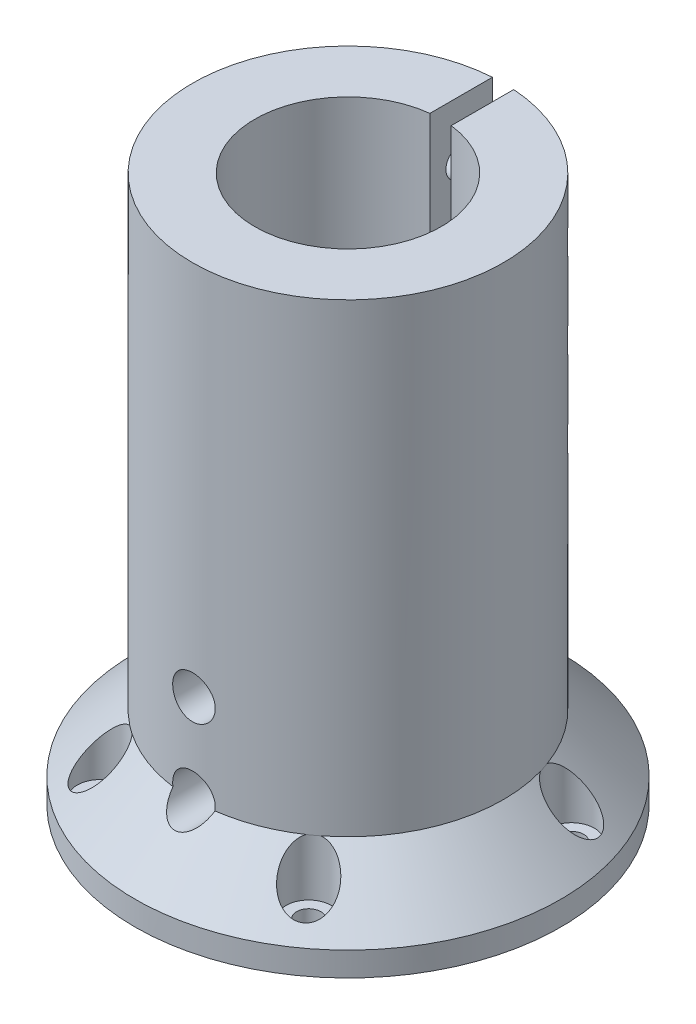
SolidWorks part; units mm, degrees
ref_plane "Front Plane" through (0, 0, 0) normal (0, 0, 1) x (1, 0, 0)
ref_plane "Top Plane" through (0, 0, 0) normal (0, 1, 0) x (1, 0, 0)
ref_plane "Right Plane" through (0, 0, 0) normal (1, 0, 0) x (0, 0, -1)
sketch "Sketch1" plane through (0, 0, 0) normal (0, 1, 0) x (1, 0, 0)
  circle A0 centre (0, 0) radius 25 construction
  circle A1 centre (0, 25) radius 1.7
  circle A2 centre (23.7764, 7.7254) radius 1.7
  circle A3 centre (14.6946, -20.2254) radius 1.7
  circle A4 centre (-14.6946, -20.2254) radius 1.7
  circle A5 centre (-23.7764, 7.7254) radius 1.7
  circle A6 centre (0, 0) radius 30
  circle A7 centre (0, 0) radius 17.5
  point P16 (0, 0)
  dimension "D1" = 50
  dimension "D2" = 3.4
  dimension "D4" = 60
  dimension "D5" = 35
  dimension "D3" = 5
extrude "Boss-Extrude1" add sketch "Sketch1" along normal blind 3
sketch "Sketch2" plane through (0, 3, 0) normal (0, 1, 0) x (1, 0, 0)
  circle A0 centre (0, 25) radius 3.1 construction
  circle A1 centre (0, 0) radius 21.9
  circle A2 centre (0, 0) radius 17.5 construction
  circle A3 centre (0, 0) radius 17.5
  dimension "D1" = 6.2
extrude "Boss-Extrude2" add sketch "Sketch2" along normal blind 32 from surface starting at face at (0, 0, 30)
chamfer "Chamfer1" distance 8.5 angle 45 1 edges at (0, 3, 21.9)
ref_plane "Plane1" through (0, 11.5, 0) normal (0, -1, 0) x (-1, 0, 0)
sketch "Sketch3" plane through (0, 11.5, 0) normal (0, -1, 0) x (-1, 0, 0)
  circle A0 centre (0, 25) radius 1.7 construction
  circle A1 centre (0, 25) radius 1.7
  circle A2 centre (0, 25) radius 3.2
  circle A3 centre (23.7764, 7.7254) radius 3.2
  circle A4 centre (14.6946, -20.2254) radius 3.2
  circle A5 centre (-14.6946, -20.2254) radius 3.2
  circle A6 centre (-23.7764, 7.7254) radius 3.2
  circle A7 centre (-23.7764, 7.7254) radius 1.7 construction
  circle A8 centre (-14.6946, -20.2254) radius 1.7 construction
  circle A9 centre (14.6946, -20.2254) radius 1.7 construction
  circle A10 centre (23.7764, 7.7254) radius 1.7 construction
  circle A11 centre (-23.7764, 7.7254) radius 1.7
  circle A12 centre (-14.6946, -20.2254) radius 1.7
  circle A13 centre (14.6946, -20.2254) radius 1.7
  circle A14 centre (23.7764, 7.7254) radius 1.7
  point P15 (0, 0)
  dimension "D2" = 5
  dimension "D1" = 1.5
extrude "Cut-Extrude3" cut sketch "Sketch3" along normal blind 8
sketch "Sketch4" plane through (0, 0, 0) normal (0, 0, 1) x (1, 0, 0)
  line L0 (0, 12) -> (0, 0) construction
  line L1 (0, 0) -> (0, 24) construction
  circle A0 centre (0, 12) radius 3
  circle A1 centre (0, 24) radius 3
  dimension "D1" = 6
  dimension "D3" = 24
  dimension "D2" = 12
extrude "Cut-Extrude4" cut sketch "Sketch4" along normal through all
sketch "Sketch5" plane through (0, 32, 0) normal (0, 1, 0) x (1, 0, 0)
  circle A0 centre (0, 0) radius 13.125
  circle A1 centre (0, 0) radius 21.9 construction
  circle A2 centre (0, 0) radius 21.9
  dimension "D1" = 26.25
extrude "Boss-Extrude3" add sketch "Sketch5" along normal blind 45
chamfer "Chamfer2" distance 4.5 angle 45 1 edges at (0, 32, 17.5)
sketch "Sketch6" plane through (0, 77, 0) normal (0, 1, 0) x (1, 0, 0)
  line L0 (0, 13.125) -> (0, 0) construction
  line L1 (-1.5, 4.35) -> (1.5, 4.35)
  line L2 (-1.5, 4.35) -> (-1.5, 21.9)
  line L3 (-1.5, 21.9) -> (1.5, 21.9)
  line L4 (1.5, 4.35) -> (1.5, 21.9)
  line L5 (-1.5, 4.35) -> (1.5, 21.9) construction
  line L6 (-1.5, 21.9) -> (1.5, 4.35) construction
  circle A0 centre (0, 0) radius 13.125 construction
  circle A1 centre (0, 0) radius 21.9 construction
  point P0 (0, 13.125)
  dimension "D1" = 3
extrude "Cut-Extrude5" cut sketch "Sketch6" against normal blind 40
sketch "Sketch8" plane through (-1.5, 0, 0) normal (1, 0, 0) x (0, 0, -1)
  line L0 (17.4438, 77) -> (17.4438, 37) construction
  line L4 (21.8486, 77) -> (13.039, 77)
  line L5 (13.039, 77) -> (13.039, 37)
  line L6 (13.039, 37) -> (21.8486, 37)
  line L7 (21.8486, 37) -> (21.8486, 77)
  line L8 (21.8486, 77) -> (13.039, 77) construction
  line L9 (13.039, 77) -> (13.039, 37) construction
  line L10 (13.039, 37) -> (21.8486, 37) construction
  line L11 (21.8486, 37) -> (21.8486, 77) construction
  circle A0 centre (17.4438, 57) radius 2.15
  circle A1 centre (17.4438, 69) radius 2.15
  circle A2 centre (17.4438, 45) radius 2.15
  dimension "D2" = 4.3
  dimension "D3" = 12
  dimension "D4" = 12
  dimension "D1" = 0
extrude "Cut-Extrude6" cut sketch "Sketch8" against normal through all
sketch "Sketch9" plane through (-1.5, 0, 0) normal (1, 0, 0) x (0, 0, -1)
  circle A0 centre (17.4438, 45) radius 2.15 construction
  circle A1 centre (17.4438, 57) radius 2.15 construction
  circle A2 centre (17.4438, 69) radius 2.15 construction
  circle A21 centre (17.4438, 45) radius 2.15 construction
  circle A22 centre (17.4438, 57) radius 2.15 construction
  circle A23 centre (17.4438, 69) radius 2.15 construction
  circle A24 centre (17.4438, 45) radius 3.15
  circle A25 centre (17.4438, 57) radius 3.15
  circle A26 centre (17.4438, 69) radius 3.15
  point P12 (0, 0)
  dimension "D1" = 1
extrude "Cut-Extrude7" cut sketch "Sketch9" along normal blind 10 from offset 16 offset against normal yes
sketch "Sketch10" plane through (1.5, 0, 0) normal (-1, 0, 0) x (0, 0, 1)
  circle A0 centre (-17.4438, 45) radius 2.15 construction
  circle A1 centre (-17.4438, 57) radius 2.15 construction
  circle A2 centre (-17.4438, 69) radius 2.15 construction
  circle A3 centre (-17.4438, 45) radius 2.15 construction
  circle A4 centre (-17.4438, 57) radius 2.15 construction
  circle A5 centre (-17.4438, 69) radius 2.15 construction
  circle A6 centre (-17.4438, 45) radius 1.75
  circle A7 centre (-17.4438, 57) radius 1.75
  circle A8 centre (-17.4438, 69) radius 1.75
  dimension "D1" = 0.4
extrude "Cut-Extrude8" cut sketch "Sketch10" against normal through all
sketch "Sketch11" plane through (1.5, 0, 0) normal (-1, 0, 0) x (0, 0, 1)
  circle A0 centre (-17.4438, 45) radius 1.75 construction
  circle A1 centre (-17.4438, 57) radius 1.75 construction
  circle A2 centre (-17.4438, 69) radius 1.75 construction
  circle A3 centre (-17.4438, 45) radius 1.75 construction
  circle A4 centre (-17.4438, 57) radius 1.75 construction
  circle A5 centre (-17.4438, 69) radius 1.75 construction
  circle A6 centre (-17.4438, 45) radius 3
  circle A7 centre (-17.4438, 57) radius 3
  circle A8 centre (-17.4438, 69) radius 3
  dimension "D1" = 1.25
extrude "Cut-Extrude9" cut sketch "Sketch11" along normal blind 14 from offset 20 offset against normal yes
